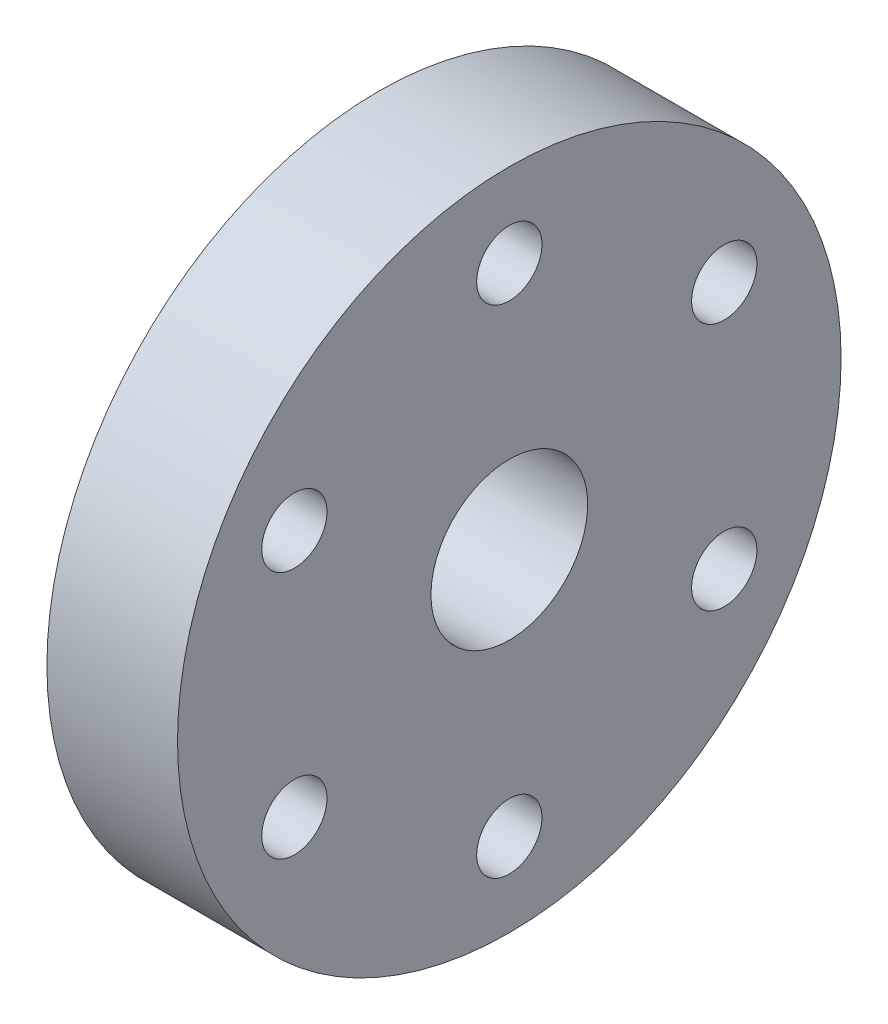
SolidWorks part; units mm, degrees
ref_plane "Front Plane" through (0, 0, 0) normal (0, 0, 1) x (1, 0, 0)
ref_plane "Top Plane" through (0, 0, 0) normal (0, 1, 0) x (1, 0, 0)
ref_plane "Right Plane" through (0, 0, 0) normal (1, 0, 0) x (0, 0, -1)
sketch "Sketch1" plane through (0, 0, 0) normal (0, 0, 1) x (1, 0, 0)
  line L0 (0, 3) -> (0, 6)
  line L1 (0, 6) -> (4.2, 6)
  line L2 (4.2, 6) -> (4.2, 12.7)
  line L3 (4.2, 12.7) -> (9.2, 12.7)
  line L4 (9.2, 12.7) -> (9.2, 3)
  line L5 (9.2, 3) -> (0, 3)
  line L6 (0, 0) -> (9.2, 0) construction
  dimension "D1" = 5
  dimension "D2" = 4.2
  dimension "D3" = 12.7
  dimension "D4" = 6
  dimension "D5" = 3
revolve "Revolve1" add sketch "Sketch1" angle 360 about L6
hole_wizard "Tap Drill for M3x0.5 Tap1" positions "Sketch3" profile "Sketch2" hole size "M3x0.5" standard "ANSI Metric" end condition up to next
sketch "Sketch3" plane through (4.2, 0, 0) normal (-1, 0, 0) x (0, 0, 1)
  point P0 (0, 9.5)
  dimension "D1" = 9.5
sketch "Sketch2" plane through (4.2, 9.5, 0) normal (0, 1, 0) x (0, 0, 1)
  line L0 (0, 0) -> (0, 5.001)
  line L1 (0, 5.001) -> (1.25, 5.001)
  line L2 (1.25, 5.001) -> (1.25, 0)
  line L5 (1.25, 0) -> (0, 0)
  line L11 (0, -6.35) -> (0, 107.95) construction
  dimension "Thru Hole Dia." = 2.5
  dimension "Thru Hole Depth" = 5.001
pattern_circular "CirPattern1" count 6 over 360 about axis through (4.2, 0, 0) along (-1, 0, 0) of "Tap Drill for M3x0.5 Tap1"
